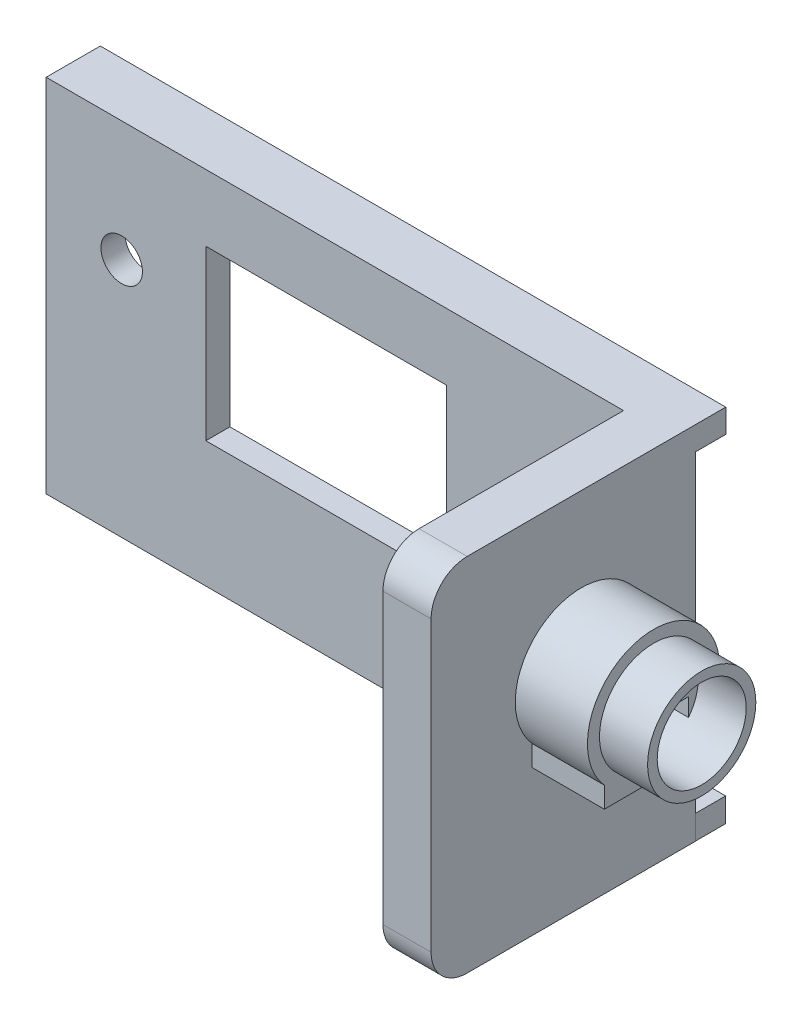
SolidWorks part; units mm, degrees
ref_plane "Front Plane" through (0, 0, 0) normal (0, 0, 1) x (1, 0, 0)
ref_plane "Top Plane" through (0, 0, 0) normal (0, 1, 0) x (1, 0, 0)
ref_plane "Right Plane" through (0, 0, 0) normal (1, 0, 0) x (0, 0, -1)
sketch "Sketch1" plane through (0, 0, 0) normal (0, 0, 1) x (1, 0, 0)
  line L1 (0, 0) -> (52, 0)
  line L2 (0, 0) -> (0, -30)
  line L3 (0, -30) -> (52, -30)
  line L4 (52, 0) -> (52, -30)
  dimension "D1" = 52
  dimension "D2" = 30
extrude "Boss-Extrude1" add sketch "Sketch1" along normal blind 2
ref_plane "Plane1" through (0, 0, 2) normal (0, 0, -1) x (-1, 0, 0)
sketch "Sketch2" plane through (0, 0, 2) normal (0, 0, -1) x (-1, 0, 0)
  line L1 (-48, 0) -> (-52, 0)
  line L2 (-48, 0) -> (-48, -30)
  line L3 (-48, -30) -> (-52, -30)
  line L4 (-52, 0) -> (-52, -30)
  dimension "D1" = 4
extrude "Boss-Extrude2" add sketch "Sketch2" against normal blind 20
fillet "Fillet1" radius 3 2 edges at (50, -30, 22) (50, 0, 22)
sketch "Sketch4" plane through (0, 0, 2) normal (0, 0, 1) x (1, 0, 0)
  line L0 (48, 0) -> (0, 0) construction
  circle A0 centre (41.2777, -10) radius 1.725
  circle A1 centre (6.2777, -10) radius 1.725
  dimension "D1" = 35
  dimension "D2" = 10
  dimension "D3" = 10
extrude "Cut-Extrude2" cut sketch "Sketch4" against normal up to surface (2 mm away) up to face at (26, -15, 0)
sketch "Sketch5" plane through (0, 0, 0) normal (0, 0, -1) x (-1, 0, 0)
  line L0 (0, -15) -> (10.3678, -15) construction
  line L5 (0, 0) -> (0, -30) construction
  line L6 (0, 0) -> (0, -30) construction
  line L7 (-51.9884, -30) -> (0, -30)
  line L8 (-51.9884, -30) -> (-51.9884, -28)
  line L9 (-51.9884, -28) -> (0, -28)
  line L10 (0, -30) -> (0, -28)
  line L12 (-52, -1.966) -> (0, -2.1935)
  line L13 (0, 0) -> (0, -2.1935)
  line L14 (-52, 0) -> (0, 0)
  line L15 (-52, 0) -> (-52, -1.966)
  point P16 (-48, -28)
  point P17 (-48, -30)
  point P18 (-52, -1.2997)
  point P19 (0, -2.1935)
  point P20 (0, 0)
  point P21 (-52, 0)
  point P23 (-52, -1.966)
  point P25 (0, 0)
  dimension "D1" = 2
extrude "Boss-Extrude3" add sketch "Sketch5" along normal blind 2.5
sketch "Sketch6" plane through (0, 0, 2) normal (0, 0, 1) x (1, 0, 0)
  line L1 (33.2777, -5.531) -> (13.2777, -5.531)
  line L2 (33.2777, -5.531) -> (33.2777, -19.531)
  line L3 (33.2777, -19.531) -> (13.2777, -19.531)
  line L4 (13.2777, -5.531) -> (13.2777, -19.531)
  circle A0 centre (6.2777, -10) radius 1.725 construction
  dimension "D3" = 7
  dimension "D1" = 14
  dimension "D2" = 20
extrude "Cut-Extrude3" cut sketch "Sketch6" against normal up to surface (2 mm away) up to face at (43.0027, -10, 0)
sketch "Sketch7" plane through (52, 0, 0) normal (1, 0, 0) x (0, 0, -1)
  line L0 (-22, -15) -> (2.0181, -15) construction
  line L1 (-12.4, -16.7) -> (-6.6, -16.7)
  line L2 (-12.4, -16.7) -> (-12.4, -13.3)
  line L3 (-12.4, -13.3) -> (-6.6, -13.3)
  line L4 (-6.6, -16.7) -> (-6.6, -13.3)
  line L5 (-22, -3) -> (-22, -27) construction
  line L6 (-9.5, -30) -> (-9.5, 5.4647) construction
  line L7 (-19, -30) -> (0, -30) construction
  line L8 (-13.6, -12.1) -> (-5.4, -12.1)
  line L9 (-5.4, -17.9) -> (-5.4, -12.1)
  line L10 (-13.6, -17.9) -> (-5.4, -17.9)
  line L11 (-13.6, -17.9) -> (-13.6, -12.1)
  dimension "D5" = 1.2
  dimension "D1" = 5.8
  dimension "D2" = 3.4
  dimension "D3" = 1.7
  dimension "D4" = 2.9
sketch "Sketch8" plane through (52, 0, 0) normal (1, 0, 0) x (0, 0, -1)
  line L0 (-9.5, -12.5) -> (-9.5, 10.2333) construction
  circle A0 centre (-9.5, -12.5) radius 4.25
  circle A1 centre (-9.5, -12.5) radius 5.5
extrude "Boss-Extrude4" add sketch "Sketch7" along normal blind 6
extrude "Boss-Extrude5" add sketch "Sketch8" along normal blind 6
sketch "Sketch10" plane through (52, 0, 0) normal (1, 0, 0) x (0, 0, -1)
  line L0 (-9.5, -14.2) -> (-9.5, 2.6372) construction
  line L2 (-12.4, -12.5) -> (-2.926, -12.5) construction
  circle A0 centre (-9.5, -12.5) radius 4.5
  circle A1 centre (-9.5, -12.5) radius 3.7
extrude "Boss-Extrude6" add sketch "Sketch10" along normal blind 10
